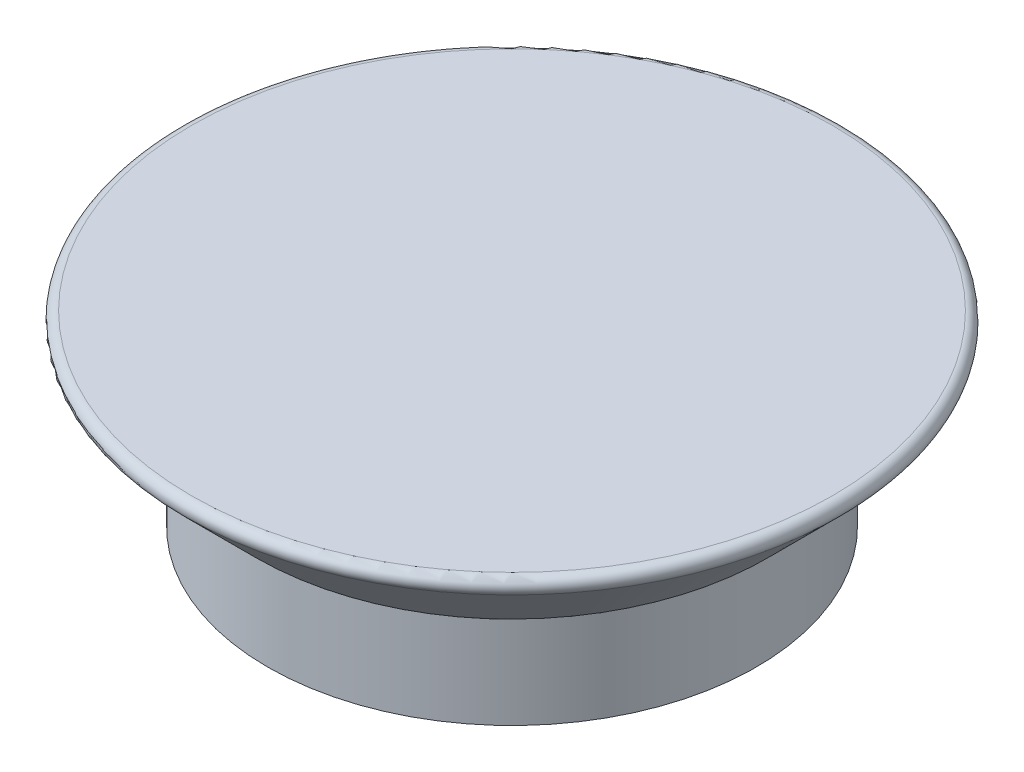
SolidWorks part; units mm, degrees
ref_plane "Front Plane" through (0, 0, 0) normal (0, 0, 1) x (1, 0, 0)
ref_plane "Top Plane" through (0, 0, 0) normal (0, 1, 0) x (1, 0, 0)
ref_plane "Right Plane" through (0, 0, 0) normal (1, 0, 0) x (0, 0, -1)
sketch "Sketch1" plane through (0, 0, 0) normal (0, 1, 0) x (1, 0, 0)
  circle A0 centre (0, 0) radius 275
  dimension "D1" = 550
extrude "Boss-Extrude1" add sketch "Sketch1" along normal blind 110
sketch "Sketch2" plane through (0, 110, 0) normal (0, 1, 0) x (1, 0, 0)
  circle A0 centre (0, 0) radius 375
  dimension "D1" = 750
extrude "Boss-Extrude2" add sketch "Sketch2" along normal blind 100
chamfer "Chamfer1" distance 90 angle 45 1 edges at (0, 110, 375)
fillet "Fillet1" radius 10 2 edges at (0, 110, 285) (0, 210, 375)
fillet "Fillet2" radius 10 1 edges at (0, 200, 375)
